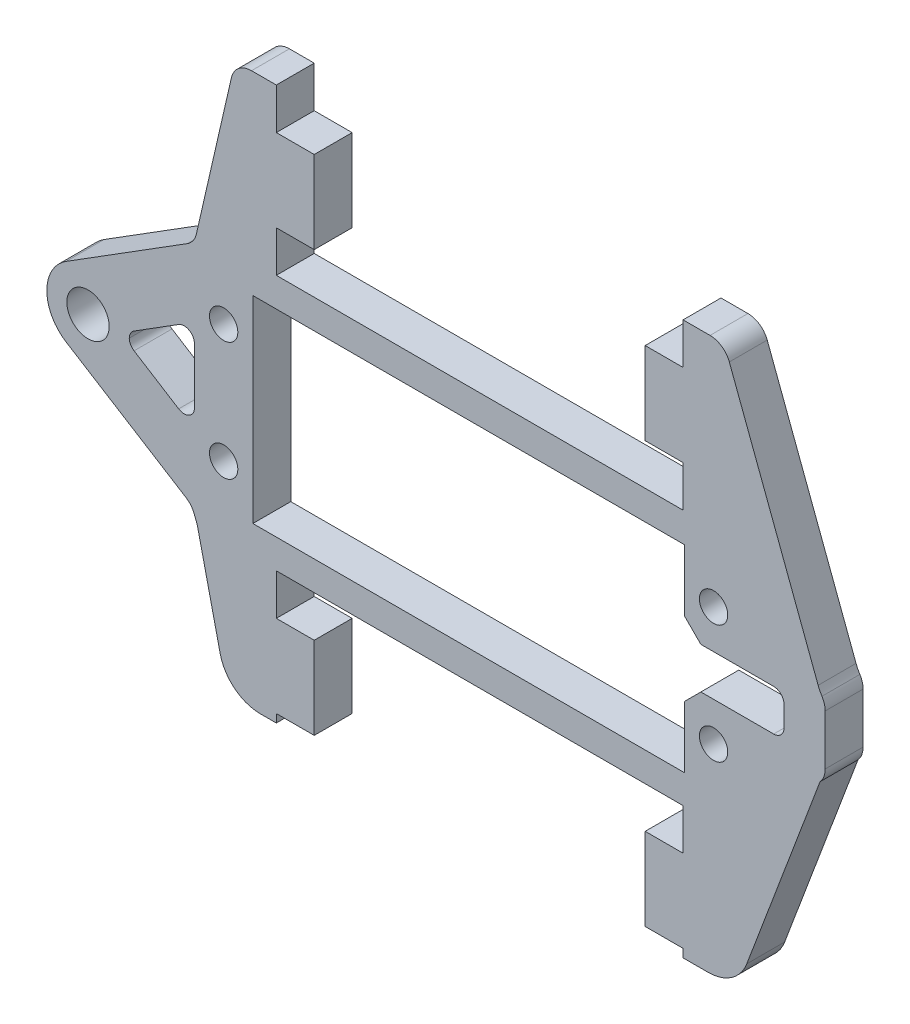
SolidWorks part; units mm, degrees
ref_plane "Front Plane" through (0, 0, 0) normal (0, 0, 1) x (1, 0, 0)
ref_plane "Top Plane" through (0, 0, 0) normal (0, 1, 0) x (1, 0, 0)
ref_plane "Right Plane" through (0, 0, 0) normal (1, 0, 0) x (0, 0, -1)
sketch "Sketch1" plane through (0, 0, 0) normal (0, 0, 1) x (1, 0, 0)
  line L0 (4.5, 30.426) -> (4.5, 0) construction
  line L1 (0, 0) -> (-66.494, 0) construction
  line L2 (0, 0) -> (0, 30.426) construction
  line L3 (0, 30.426) -> (-66.494, 30.426) construction
  line L4 (-66.494, 0) -> (-66.494, 30.426) construction
  line L5 (9, 15.213) -> (0, 15.213) construction
  line L6 (-33.247, 30.426) -> (-33.247, 0) construction
  line L7 (-70.994, 30.426) -> (-70.994, 0) construction
  line L8 (-75.494, 15.213) -> (-66.494, 15.213) construction
  line L9 (-75.494, 0) -> (-75.494, 30.426)
  line L10 (9, 0) -> (9, 30.426)
  line L11 (-75.494, 0) -> (-77.5948, -11.5651)
  line L12 (-33.247, 0) -> (-33.247, -4.5) construction
  line L13 (-7.847, -4.5) -> (-58.647, -4.5)
  line L14 (-58.647, -9) -> (-58.647, 0)
  line L15 (-58.647, -4.5) -> (-65.9804, -16.0944)
  line L16 (4.5, 34.926) -> (-70.994, 34.926)
  line L17 (9, 0) -> (11.1008, -11.5651)
  line L18 (-7.847, -4.5) -> (-0.5136, -16.0944)
  line L20 (0, 0) -> (-66.494, 0)
  line L21 (0, 0) -> (0, 30.426)
  line L22 (0, 30.426) -> (-66.494, 30.426)
  line L23 (-66.494, 0) -> (-66.494, 30.426)
  circle A0 centre (4.5, 24.357) radius 2.413 construction
  circle A1 centre (4.5, 6.069) radius 2.413 construction
  circle A2 centre (-70.994, 6.069) radius 2.413 construction
  circle A3 centre (-70.994, 24.357) radius 2.413 construction
  circle A4 centre (-71.347, -12.7) radius 3.175 construction
  circle A5 centre (4.853, -12.7) radius 3.175 construction
  arc A6 (-77.5948, -11.5651) -> (-65.9804, -16.0944) centre (-71.347, -12.7) ccw
  arc A7 (-75.494, 30.426) -> (-70.994, 34.926) centre (-70.994, 30.426) cw
  arc A8 (9, 30.426) -> (4.5, 34.926) centre (4.5, 30.426) ccw
  circle A9 centre (4.853, -12.7) radius 3.175 construction
  arc A10 (11.1008, -11.5651) -> (-0.5136, -16.0944) centre (4.853, -12.7) cw
  point P12 (4.5, 15.213)
  point P31 (-75.494, 15.213)
  point P39 (-33.247, -4.5)
  point P42 (-58.647, -4.5)
  dimension "D3" = 4.5
  dimension "D4" = 12.7
  dimension "D6" = 12.7
  dimension "D1" = 66.494
  dimension "D2" = 30.426
  dimension "D5" = 38.1
  dimension "D7" = 4.5
  dimension "D8" = 25.4
  dimension "D9" = 9.144
extrude "Boss-Extrude1" add sketch "Sketch1" along normal blind 5.842 contours A10 L17 L10 A8 L16 A7 L9 L11 A6 L15 L13 L18 region at (-74.454, 15.213, 0)
hole_wizard "11/64 (0.17188) Diameter Hole1" positions "Sketch3" profile "Sketch2" hole size "11/64" standard "ANSI Inch" end condition through all
sketch "Sketch3" plane through (0, 0, 5.842) normal (0, 0, 1) x (1, 0, 0)
  line L1 (-66.494, 15.213) -> (-75.494, 15.213) construction
  line L2 (-66.494, 0) -> (-66.494, 30.426) construction
  line L3 (-75.494, 0) -> (-75.494, 30.426) construction
  point P0 (-70.994, 24.357)
  point P2 (-70.994, 6.069)
  dimension "D1" = 9.144
  dimension "D2" = 9.144
  dimension "D3" = 4.5
  dimension "D4" = 4.5
sketch "Sketch2" plane through (-70.994, 24.357, 5.842) normal (1, 0, 0) x (0, -1, 0)
  line L0 (0, 0) -> (0, 5.842)
  line L1 (0, 5.842) -> (2.1829, 5.842)
  line L2 (2.1829, 5.842) -> (2.1829, 0)
  line L5 (2.1829, 0) -> (0, 0)
  line L11 (0, -6.35) -> (0, 107.95) construction
  dimension "Thru Hole Dia." = 4.3658
  dimension "Thru Hole Depth" = 5.842
sketch "Sketch4" plane through (0, 0, 5.842) normal (0, 0, 1) x (1, 0, 0)
  line L0 (-33.247, 34.926) -> (-33.247, -4.5) construction
  line L1 (4.5, 34.926) -> (-70.994, 34.926) construction
  line L2 (-7.847, -4.5) -> (-58.647, -4.5) construction
ref_plane "Plane1" through (-33.247, 0, 0) normal (-1, 0, 0) x (0, 0, 1)
mirror "Mirror1" about plane through (-33.247, 0, 0) normal (-1, 0, 0) of "11/64 (0.17188) Diameter Hole1"
hole_wizard "F (0.257) Diameter Hole1" positions "Sketch6" profile "Sketch5" hole size "F" standard "ANSI Inch" end condition through all
sketch "Sketch6" plane through (0, 0, 5.842) normal (0, 0, 1) x (1, 0, 0)
  arc A0 (-77.5948, -11.5651) -> (-65.9804, -16.0944) centre (-71.347, -12.7) ccw construction
  point P0 (-71.347, -12.7)
  point P3 (-73.6541, -18.6161)
  dimension "D1" = 6.35
  dimension "D2" = 6.35
sketch "Sketch5" plane through (-71.347, -12.7, 5.842) normal (1, 0, 0) x (0, -1, 0)
  line L0 (0, 0) -> (0, 5.842)
  line L1 (0, 5.842) -> (3.2639, 5.842)
  line L2 (3.2639, 5.842) -> (3.2639, 0)
  line L5 (3.2639, 0) -> (0, 0)
  line L11 (0, -6.35) -> (0, 107.95) construction
  dimension "Thru Hole Dia." = 6.5278
  dimension "Thru Hole Depth" = 5.842
mirror "Mirror2" about plane through (-33.247, 0, 0) normal (-1, 0, 0) of "F (0.257) Diameter Hole1"
sketch "Sketch10" plane through (0, 0, 5.842) normal (0, 0, 1) x (1, 0, 0)
  line L0 (-66.494, 15.213) -> (-93.2951, 15.213) construction
  line L1 (-66.494, 0) -> (-66.494, 30.426) construction
  line L2 (-95.2673, 20.5929) -> (-73.3845, 34.314)
  line L3 (-95.2673, 9.8331) -> (-75.9013, -2.2426)
  line L4 (-75.9013, -2.2426) -> (-75.494, 0)
  line L5 (-75.494, 0) -> (-77.5948, -11.5651) construction
  line L6 (-75.494, 0) -> (-75.494, 8.0575)
  line L7 (-75.494, 0) -> (-75.494, 30.426) construction
  line L8 (-85.5972, 16.0334) -> (-75.494, 22.3685)
  line L9 (-85.5972, 14.3926) -> (-75.494, 8.0575)
  line L10 (-75.494, 22.3685) -> (-75.494, 30.426)
  line L11 (-73.3845, 34.314) -> (-68.6034, 34.314)
  line L12 (-75.494, 30.426) -> (-68.6034, 34.314)
  circle A0 centre (-91.894, 15.213) radius 3.175 construction
  arc A1 (-95.2673, 20.5929) -> (-95.2673, 9.8331) centre (-91.894, 15.213) ccw
  circle A2 centre (-70.994, 30.5015) radius 4.5 construction
  arc A3 (-85.5972, 14.3926) -> (-85.5972, 16.0334) centre (-91.894, 15.213) ccw
  point P19 (-90.4862, 17.4581)
  point P20 (-68.6034, 3.737)
  point P21 (-90.4862, 12.9679)
  point P22 (-68.6034, 26.689)
  dimension "D1" = 25.4
  dimension "D2" = 6.35
  dimension "D3" = 12.7
  dimension "D4" = 4.5
  dimension "D5" = 9
extrude "Boss-Extrude3" add sketch "Sketch10" against normal up to surface (5.842 mm away) up to face at (8.1169, -12.7, 0)
hole_wizard "F (0.257) Diameter Hole3" positions "Sketch12" profile "Sketch11" hole size "F" standard "ANSI Inch" end condition through all
sketch "Sketch12" plane through (0, 0, 5.842) normal (0, 0, 1) x (1, 0, 0)
  line L0 (-66.494, 15.213) -> (-91.894, 15.213) construction
  line L1 (-66.494, 0) -> (-66.494, 30.426) construction
  point P2 (-91.894, 15.213)
  dimension "D1" = 25.4
sketch "Sketch11" plane through (-91.894, 15.213, 5.842) normal (1, 0, 0) x (0, -1, 0)
  line L0 (0, 0) -> (0, 5.842)
  line L1 (0, 5.842) -> (3.2639, 5.842)
  line L2 (3.2639, 5.842) -> (3.2639, 0)
  line L5 (3.2639, 0) -> (0, 0)
  line L11 (0, -6.35) -> (0, 107.95) construction
  dimension "Thru Hole Dia." = 6.5278
  dimension "Thru Hole Depth" = 5.842
sketch "Sketch13" plane through (0, 0, 5.842) normal (0, 0, 1) x (1, 0, 0)
  line L0 (0, 15.213) -> (9, 15.213) construction
  line L1 (0, 0) -> (0, 30.426) construction
  line L2 (9, 0) -> (9, 30.426) construction
  line L4 (0, 18.388) -> (9, 18.388)
  line L5 (0, 18.388) -> (0, 12.038)
  line L6 (0, 12.038) -> (9, 12.038)
  line L7 (9, 18.388) -> (9, 12.038)
  dimension "D1" = 6.35
extrude "Cut-Extrude1" cut sketch "Sketch13" against normal through all
chamfer "Chamfer1" distance 2.54 angle 45 2 edges at (0, 12.038, 2.921) (0, 18.388, 2.921)
sketch "Sketch22" plane through (0, 0, 5.842) normal (0, 0, 1) x (1, 0, 0)
  line L0 (9, 18.388) -> (9, 24.738)
  line L1 (9, 18.388) -> (9, 30.426) construction
  line L2 (9, 12.038) -> (9, 5.688)
  line L3 (9, 0) -> (9, 12.038) construction
  line L4 (9, 18.388) -> (15.35, 18.388)
  line L5 (9, 12.038) -> (15.35, 12.038)
  line L6 (15.35, 12.038) -> (15.35, 18.388)
  line L7 (21.7, 21.563) -> (21.7, 8.863)
  line L8 (15.35, 15.213) -> (21.7, 15.213) construction
  line L9 (21.7, 8.863) -> (9, 5.688)
  line L10 (21.7, 21.563) -> (9, 24.738)
  point P14 (21.7, 15.213)
  dimension "D1" = 6.35
  dimension "D2" = 6.35
  dimension "D3" = 6.35
  dimension "D4" = 6.35
  dimension "D5" = 12.7
  dimension "D6" = 12.7
extrude "Boss-Extrude6" add sketch "Sketch22" against normal up to surface (5.842 mm away) up to face at (-88.6301, 15.213, 0)
fillet "Fillet1" radius 3.175 4 edges at (21.7, 21.563, 2.921) (21.7, 8.863, 2.921) (9, 5.688, 2.921) (9, 24.738, 2.921)
fillet "Fillet2" radius 1.5875 2 edges at (15.35, 18.388, 2.921) (15.35, 12.038, 2.921)
fillet "Fillet3" radius 1.5875 4 edges at (-75.494, 8.0575, 2.921) (-75.494, 22.3685, 2.921) (-85.5972, 14.3926, 2.921) (-85.5972, 16.0334, 2.921)
sketch "Sketch24" plane through (0, 0, 0) normal (0, 0, -1) x (-1, 0, 0)
  line L0 (33.247, -3.2131) -> (33.247, 3.2131) construction
  line L1 (6.0426, 48.7944) -> (57.0376, 48.7944) construction
  line L2 (6.0426, 48.7944) -> (6.0426, 34.926) construction
  line L3 (6.0426, 34.926) -> (57.0376, 34.926) construction
  line L4 (57.0376, 48.7944) -> (57.0376, 41.276)
  line L5 (6.0426, 48.7944) -> (57.0376, 34.926) construction
  line L6 (6.0426, 34.926) -> (57.0376, 48.7944) construction
  line L7 (33.247, 34.926) -> (33.247, 62.71) construction
  line L8 (-4.5, 34.926) -> (70.994, 34.926) construction
  line L9 (62.8796, 53.976) -> (62.8796, 60.326)
  line L10 (57.0376, 41.276) -> (62.8796, 41.276)
  line L11 (57.0376, 48.7944) -> (57.0376, 53.976)
  line L12 (57.0376, 53.976) -> (62.8796, 53.976)
  line L13 (62.8796, 60.326) -> (69.2296, 60.326)
  line L14 (75.494, 15.213) -> (75.494, 69.8025) construction
  line L15 (75.494, 10.9267) -> (75.494, 19.4993) construction
  line L16 (69.2296, 60.326) -> (75.494, 32.9914)
  line L17 (73.3845, 34.314) -> (95.2673, 20.5929) construction
  line L18 (73.3845, 34.314) -> (75.494, 32.9914)
  line L19 (62.8796, 41.276) -> (62.8796, 34.926)
  line L20 (62.8796, 34.926) -> (70.994, 34.926)
  line L21 (73.3845, 34.314) -> (73.2596, 34.314)
  line L22 (70.994, 34.926) -> (73.2596, 34.314)
  line L23 (57.0376, 34.926) -> (57.0376, 48.7944) construction
  line L24 (66.494, 0) -> (66.494, 30.426) construction
  line L25 (31.5401, 34.926) -> (31.5401, 48.7944) construction
  line L26 (0.2006, 60.326) -> (-6.1494, 60.326)
  line L27 (0.2006, 41.276) -> (0.2006, 34.926)
  line L28 (0.2006, 53.976) -> (0.2006, 60.326)
  line L29 (6.0426, 41.276) -> (0.2006, 41.276)
  line L30 (6.0426, 48.7944) -> (6.0426, 41.276)
  line L31 (6.0426, 48.7944) -> (6.0426, 53.976)
  line L32 (6.0426, 53.976) -> (0.2006, 53.976)
  line L33 (-6.1494, 60.326) -> (-21.7, 19.084)
  line L34 (0.2006, 34.926) -> (-9.6993, 22.9997)
  line L35 (-9.6993, 22.9997) -> (-21.7, 19.084)
  arc A0 (-19.295, 22.1642) -> (-21.7, 19.084) centre (-18.525, 19.084) ccw construction
  point P0 (31.5401, 41.8602)
  dimension "D1" = 50.995
  dimension "D2" = 13.8684
  dimension "D3" = 0
  dimension "D4" = 6.35
  dimension "D5" = 5.842
  dimension "D6" = 12.7
  dimension "D7" = 6.35
  dimension "D8" = 6.35
  dimension "D9" = 9.4564
extrude "Boss-Extrude7" add sketch "Sketch24" against normal up to surface (5.842 mm away) up to face at (-23.4931, 10.695, 5.842)
fillet "Fillet4" radius 3.175 2 edges at (-75.494, 32.9914, 2.921) (-69.2296, 60.326, 2.921)
fillet "Fillet5" radius 6.35 1 edges at (20.9096, 21.1803, 2.921)
fillet "Fillet6" radius 3.175 1 edges at (6.1494, 60.326, 2.921)
chamfer "Chamfer2" [suppressed] distance 2.54 angle 45
sketch "Sketch25" [suppressed] plane through (0, 0, 0) normal (0, 0, -1) x (-1, 0, 0)
  line L0 (64.7897, 60.326) -> (65.6047, 53.976)
  line L1 (66.6999, 60.326) -> (62.8796, 60.326) construction
  line L2 (62.8796, 38.101) -> (72.4046, 38.101) construction
  line L3 (62.8796, 41.276) -> (62.8796, 34.926) construction
  line L5 (75.7072, 33.143) -> (75.7072, 60.326)
  line L6 (75.7072, 60.326) -> (64.7897, 60.326)
  line L7 (65.6047, 53.976) -> (75.7072, 33.143)
  line L9 (62.8796, 53.976) -> (70.6848, 53.976) construction
  line L10 (75.2002, 34.2734) -> (69.7947, 57.8602) construction
  arc A0 (75.2002, 34.2734) -> (76.6083, 32.2927) centre (78.295, 34.9826) ccw construction
  dimension "D1" = 9.525
extrude "Cut-Extrude2" [suppressed] cut sketch "Sketch25" against normal through all
fillet "Fillet8" [suppressed] radius 1.5875
fillet "Fillet9" [suppressed] radius 12.7
sketch "Sketch26" plane through (0, 0, 0) normal (0, 0, -1) x (-1, 0, 0)
  line L0 (-9, 0) -> (-9, 3.209) construction
  line L1 (89.1491, -30.6039) -> (-16.4452, -30.6039)
  line L2 (89.1491, -30.6039) -> (89.1491, -4.5)
  line L3 (75.9013, -4.5) -> (-9, -4.5)
  line L4 (-16.4452, -30.6039) -> (-16.4452, -4.5)
  line L6 (89.1491, -4.5) -> (89.1491, -2.2426)
  line L7 (89.1491, -2.2426) -> (75.9013, -2.2426)
  line L8 (75.9013, -4.5) -> (75.9013, -2.2426)
  line L10 (-16.4452, -4.5) -> (-16.4452, 1.6045)
  line L11 (-16.4452, 1.6045) -> (-9, 1.6045)
  line L12 (-9, -4.5) -> (-9, 1.6045)
extrude "Cut-Extrude3" cut sketch "Sketch26" against normal through all
sketch "Sketch27" plane through (0, 0, 0) normal (0, 0, -1) x (-1, 0, 0)
  line L0 (66.494, 15.213) -> (-15.35, 15.213) construction
  line L1 (66.494, 0) -> (66.494, 30.426) construction
  line L2 (-15.35, 13.6255) -> (-15.35, 16.8005) construction
ref_plane "Plane2" through (0, 15.213, 0) normal (0, -1, 0) x (-1, 0, 0)
mirror "Mirror3" about plane through (0, 15.213, 0) normal (0, -1, 0) of "Boss-Extrude7"
sketch "Sketch28" plane through (0, 0, 0) normal (0, 0, -1) x (-1, 0, 0)
  line L0 (75.0506, -4.5) -> (75.9013, -2.2426)
  line L1 (75.9013, -2.2426) -> (75.9013, -4.5)
  line L2 (75.9013, -4.5) -> (75.0506, -4.5)
extrude "Cut-Extrude4" cut sketch "Sketch28" against normal through all
fillet "Fillet10" radius 3.175 4 edges at (6.1494, -29.9, 2.921) (-69.2296, -29.9, 2.921) (-75.9013, -2.2426, 2.921) (-75.0506, -4.5, 2.921)
sketch "Sketch29" plane through (0, 0, 5.842) normal (0, 0, 1) x (1, 0, 0)
  line L0 (-62.8796, 60.326) -> (-0.2006, 60.326) construction
  line L1 (-66.6999, -29.9) -> (-62.8796, -29.9) construction
  line L2 (-75.7377, -24.82) -> (11.467, -24.82)
  line L3 (-75.7377, -24.82) -> (-75.7377, -29.9)
  line L4 (-75.7377, -29.9) -> (11.467, -29.9)
  line L5 (11.467, -24.82) -> (11.467, -29.9)
  dimension "D1" = 5.08
extrude "Cut-Extrude6" cut sketch "Sketch29" against normal through all
fillet "Fillet12" radius 6.35 2 edges at (8.0649, -24.82, 2.921) (-70.3938, -24.82, 2.921)
